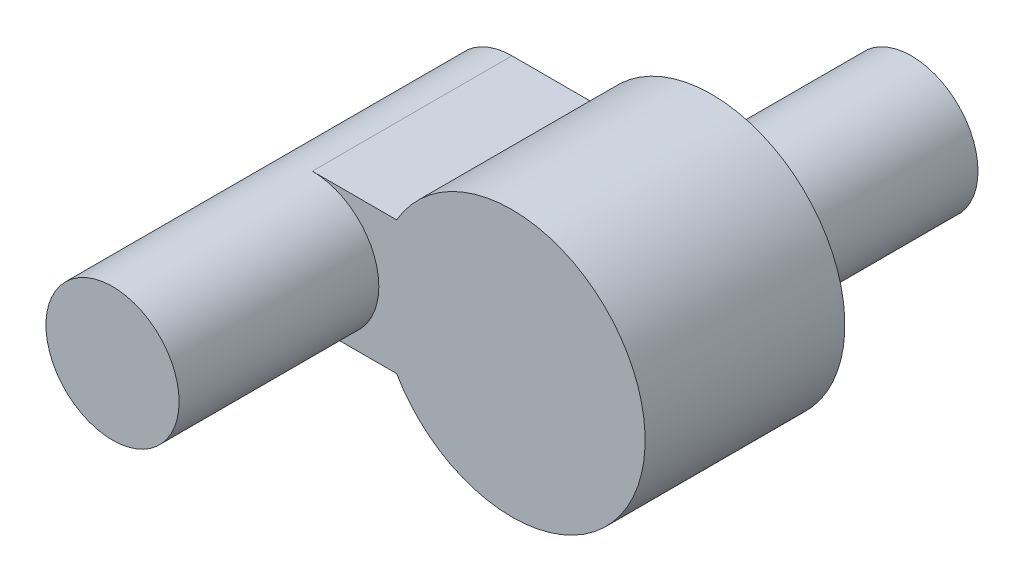
SolidWorks part; units mm, degrees
ref_plane "Спереди" through (0, 0, 0) normal (0, 0, 1) x (1, 0, 0)
ref_plane "Сверху" through (0, 0, 0) normal (0, 1, 0) x (1, 0, 0)
ref_plane "Справа" through (0, 0, 0) normal (1, 0, 0) x (0, 0, -1)
other "Configuration Table"
sketch "Sketch1" plane through (0, 0, 0) normal (0, 0, 1) x (1, 0, 0)
  line L0 (-0.5652, 4.3904) -> (-10.6356, 4.3904) construction
  line L5 (-8.7387, 5.3904) -> (-7.4707, 5.3904)
  line L6 (-8.7387, 3.3904) -> (-7.4707, 3.3904)
  circle A3 centre (-8.7387, 4.3904) radius 1
  circle A7 centre (-5.7387, 4.3904) radius 2
  point P0 (-6.5763, 4.3904)
  dimension "D1" = 4
  dimension "D2" = 2
  dimension "D3" = 2
  dimension "D4" = 3
extrude "Boss-Extrude1" add sketch "Sketch1" along normal blind 3 contours A7 L0 A3 L6 | L0 A7 L5 A3 | A3 L0 | L0 A7 | A7 L0 | A3 region at (-5.7387, 3.5416, 0) region at (-5.7387, 5.2392, 0) region at (-8.7387, 3.966, 0) region at (-7.8749, 3.6204, 0) region at (-7.8749, 5.1604, 0)
ref_plane "Plane1" through (0, 0, 3) normal (0, 0, 1) x (1, 0, 0)
sketch "Sketch2" plane through (0, 0, 3) normal (0, 0, 1) x (1, 0, 0)
  circle A0 centre (-8.7387, 4.3904) radius 1
  arc A2 (-8.7387, 5.3904) -> (-8.7387, 3.3904) centre (-8.7387, 4.3904) ccw construction
extrude "Boss-Extrude2" add sketch "Sketch2" along normal blind 3
ref_plane "Plane2" through (0, 0, 0) normal (0, 0, -1) x (-1, 0, 0)
sketch "Sketch3" plane through (0, 0, 0) normal (0, 0, -1) x (-1, 0, 0)
  circle A0 centre (5.7387, 4.3904) radius 1
  circle A1 centre (8.7387, 4.3904) radius 1 construction
extrude "Boss-Extrude3" add sketch "Sketch3" along normal blind 3
equation "\"R small\"= 2"
equation "\"R big\"= 4"
equation "\"width\"= 0.6"
equation "\"border width\"= 1"
equation "\"D1@Sketch1\"=\"R big\""
equation "\"D2@Sketch1\"=\"R small\""
equation "\"D3@Sketch1\"=\"R small\""
equation "\"depth\"= 3"
